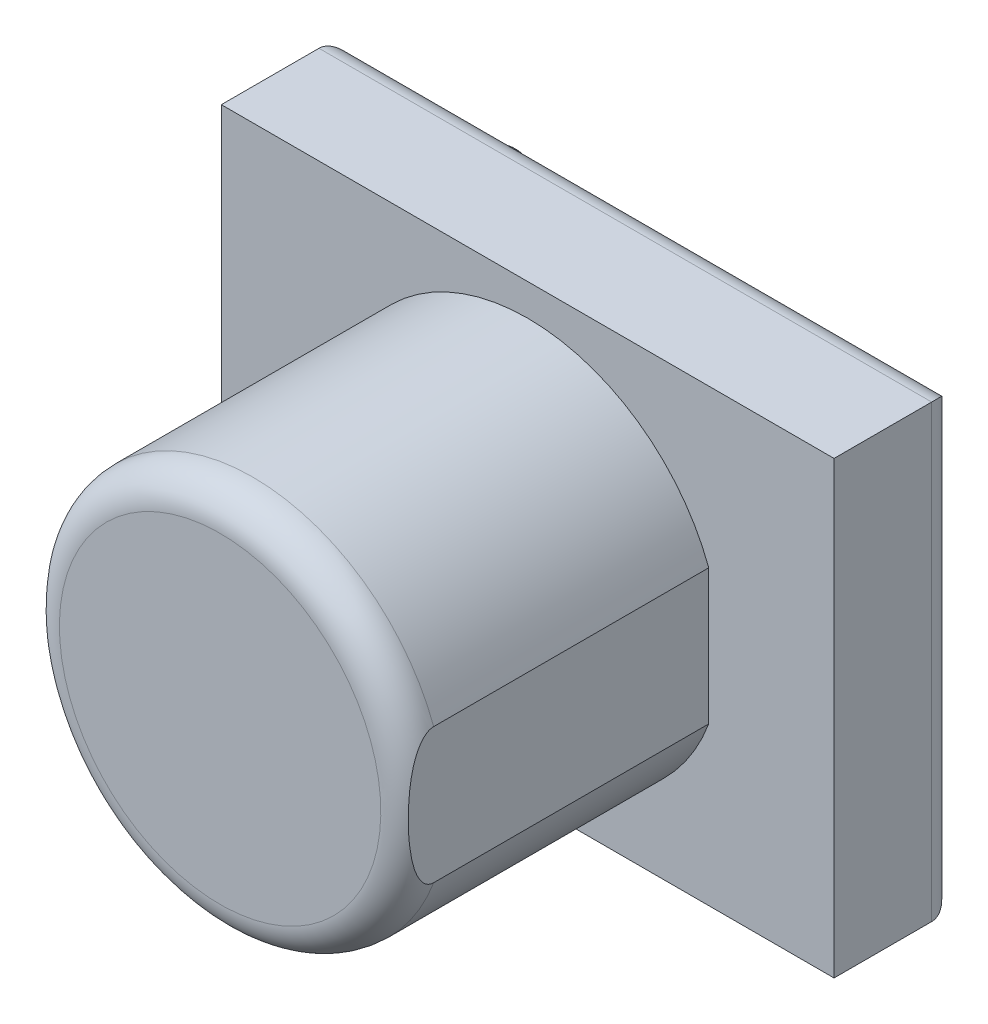
SolidWorks part; units mm, degrees
material "ABS"
ref_plane "Front Plane" through (0, 0, 0) normal (0, 0, 1) x (1, 0, 0)
ref_plane "Top Plane" through (0, 0, 0) normal (0, 1, 0) x (1, 0, 0)
ref_plane "Right Plane" through (0, 0, 0) normal (1, 0, 0) x (0, 0, -1)
sketch "Sketch1" plane through (0, 0, 0) normal (0, 0, 1) x (1, 0, 0)
  line L1 (-5.6515, -2.1099) -> (5.6515, -2.1099)
  line L2 (-5.6515, -2.1099) -> (-5.6515, 2.1099)
  line L3 (-5.6515, 2.1099) -> (5.6515, 2.1099)
  line L4 (5.6515, -2.1099) -> (5.6515, 2.1099)
  line L5 (-5.6515, -2.1099) -> (5.6515, 2.1099) construction
  line L6 (-5.6515, 2.1099) -> (5.6515, -2.1099) construction
  circle A0 centre (0, 0) radius 6.0325
  dimension "D1" = 12.065
  dimension "D2" = 11.303
extrude "Boss-Extrude1" add sketch "Sketch1" along normal blind 9.6012 contours L3 A0 | L1 L4 L3 L2 | L1 A0
sketch "Sketch2" plane through (0, 0, 0) normal (0, 0, -1) x (-1, 0, 0)
  line L1 (-9.5631, -7.0231) -> (9.5631, -7.0231)
  line L2 (-9.5631, -7.0231) -> (-9.5631, 7.0231)
  line L3 (-9.5631, 7.0231) -> (9.5631, 7.0231)
  line L4 (9.5631, -7.0231) -> (9.5631, 7.0231)
  line L5 (-9.5631, -7.0231) -> (9.5631, 7.0231) construction
  line L6 (-9.5631, 7.0231) -> (9.5631, -7.0231) construction
  point P0 (0, 0)
  dimension "D1" = 14.0462
  dimension "D2" = 19.1262
extrude "Boss-Extrude2" add sketch "Sketch2" along normal blind 3.81
sketch "Sketch3" plane through (0, 0, -3.81) normal (0, 0, -1) x (-1, 0, 0)
  line L1 (-7.4041, -4.3815) -> (7.4041, -4.3815)
  line L2 (-7.4041, -4.3815) -> (-7.4041, 4.3815)
  line L3 (-7.4041, 4.3815) -> (7.4041, 4.3815)
  line L4 (7.4041, -4.3815) -> (7.4041, 4.3815)
  line L5 (-7.4041, -4.3815) -> (7.4041, 4.3815) construction
  line L6 (-7.4041, 4.3815) -> (7.4041, -4.3815) construction
  point P0 (0, 0)
  dimension "D1" = 8.763
  dimension "D2" = 14.8082
extrude "Boss-Extrude3" add sketch "Sketch3" along normal blind 2.921
sketch "Sketch4" plane through (0, -4.3815, 0) normal (0, -1, 0) x (1, 0, 0)
  arc A0 (7.4041, -3.81) -> (-7.4041, -6.731) centre (16.7852, -90.364) ccw
extrude "Cut-Extrude1" cut sketch "Sketch4" against normal through all and the other way through all
fillet "Fillet1" radius 0.762 1 edges at (-7.4041, 0, -6.731)
fillet "Fillet2" radius 0.762 4 edges at (0, 7.0231, -3.81) (9.5631, 0, -3.81) (0, -7.0231, -3.81) (-9.5631, 0, -3.81)
fillet "Fillet3" radius 0.762 6 edges at (-7.4041, -4.3815, -4.7667) (-7.1035, -4.3815, -6.3299) (-7.4041, 4.3815, -4.7667) (-7.1035, 4.3815, -6.3299) (0.429, -4.3815, -4.8533) (0.429, 4.3815, -4.8533)
fillet "Fillet4" radius 1.016 2 edges at (0, 6.0325, 9.6012) (0, -6.0325, 9.6012)
